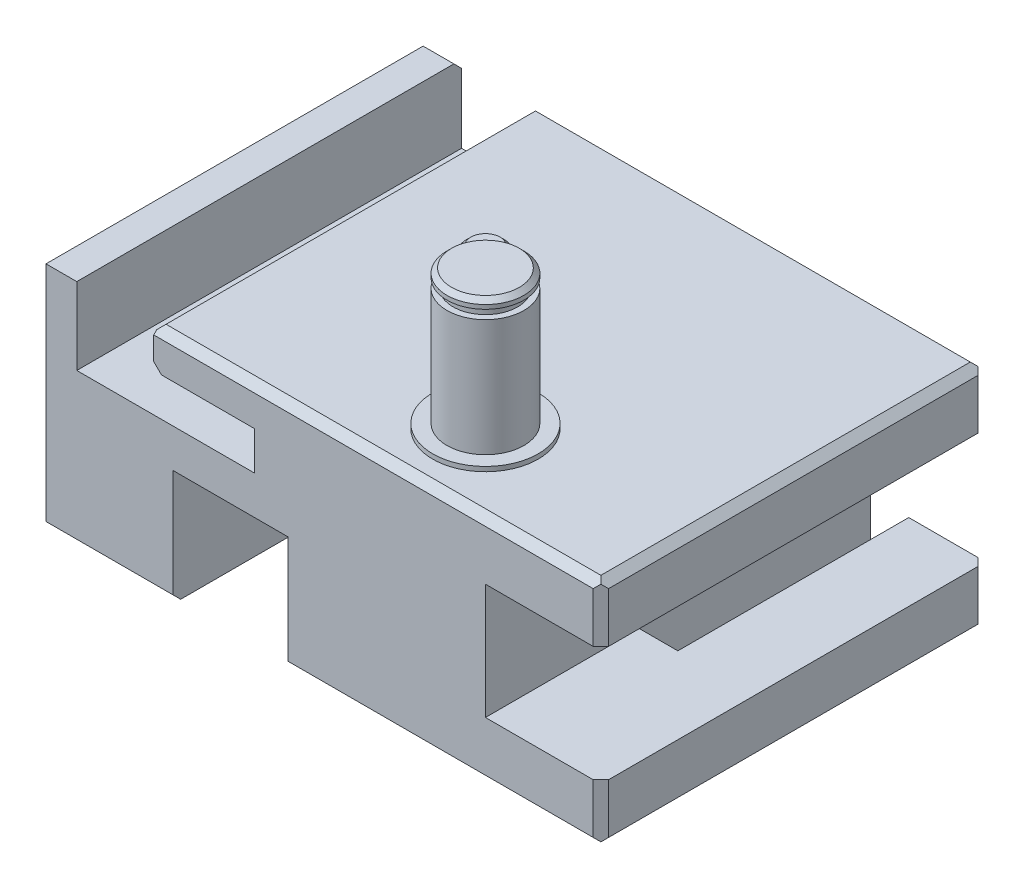
SolidWorks part; units mm, degrees
material "AISI Type A2 Tool Steel"
ref_plane "Front Plane" through (0, 0, 0) normal (0, 0, 1) x (1, 0, 0)
ref_plane "Top Plane" through (0, 0, 0) normal (0, 1, 0) x (1, 0, 0)
ref_plane "Right Plane" through (0, 0, 0) normal (1, 0, 0) x (0, 0, -1)
ref_axis "X-axis" through (-88.99, 0, 0) along (1, 0, 0)
ref_axis "Y-axis" through (0, 55, 0) along (0, -1, 0)
ref_axis "Z-axis" through (0, 0, -88.99) along (0, 0, 1)
sketch "Sketch1" plane through (0, 0, 0) normal (0, 0, 1) x (1, 0, 0)
  line L0 (27.3685, 0) -> (27.3685, 20.8848) construction
  line L1 (0, 0) -> (7.9375, 0)
  line L2 (0, 0) -> (0, 19.05)
  line L3 (0, 19.05) -> (43.2435, 19.05)
  line L4 (43.2435, 0) -> (43.2435, 19.05)
  line L5 (10.7061, 0) -> (10.7061, 19.05) construction
  line L6 (14.6685, 0) -> (14.6685, 19.05) construction
  line L7 (12.6873, -1.5141) -> (12.6873, 17.6649) construction
  line L8 (4.7498, 9.525) -> (20.6248, 9.525)
  line L9 (4.7498, 9.525) -> (4.7498, 6.35)
  line L10 (7.9375, 6.35) -> (7.9375, 0)
  line L11 (17.4371, 6.35) -> (17.4371, 0)
  line L12 (4.7498, 6.35) -> (7.9375, 6.35)
  line L13 (20.6248, 6.35) -> (17.4371, 6.35)
  line L14 (20.6248, 9.525) -> (20.6248, 6.35)
  line L15 (17.4371, 0) -> (43.2435, 0)
  point P16 (12.6873, 9.525)
  point P19 (4.7498, 9.525)
  point P22 (4.7498, 6.35)
  point P25 (7.9375, 6.35)
  dimension "D1" = 19.05
  dimension "D2" = 4.7498
  dimension "D3" = 15.875
  dimension "D4" = 16.6624
  dimension "D5" = 12.7
  dimension "D6" = 14.6812
  dimension "D7" = 15.875
  dimension "D8" = 3.175
  dimension "D9" = 9.525
  dimension "D10" = 4.7498
extrude "Boss-Extrude1" add sketch "Sketch1" along normal blind 31.75
sketch "Sketch3" plane through (0, 0, 0) normal (0, 0, 1) x (1, 0, 0)
  line L0 (6.35, 15.875) -> (14.6685, 15.875)
  line L1 (0, 0) -> (0, 19.05) construction
  line L2 (14.6685, 0) -> (14.6685, 19.05) construction
  line L3 (14.6685, 15.875) -> (14.6685, 12.7)
  line L4 (14.6685, 12.7) -> (0, 12.7)
  line L5 (4.7498, 9.525) -> (20.6248, 9.525) construction
  line L6 (0, 19.05) -> (43.2435, 19.05) construction
  line L7 (6.35, 15.875) -> (6.35, 19.05)
  line L9 (0, 12.7) -> (0, 19.05)
  line L10 (0, 19.05) -> (6.35, 19.05)
  dimension "D1" = 3.175
  dimension "D2" = 3.175
  dimension "D3" = 6.35
extrude "Cut-Extrude2" cut sketch "Sketch3" along normal through all
sketch "Sketch2" plane through (0, 0, 0) normal (0, 0, 1) x (1, 0, 0)
  line L0 (25.3873, 0) -> (43.2435, 9.525)
  line L1 (17.4371, 0) -> (43.2435, 0) construction
  line L2 (43.2435, 0) -> (43.2435, 19.05) construction
  line L3 (43.2435, 19.05) -> (6.35, 19.05) construction
  line L4 (20.6248, 9.525) -> (20.6248, 6.35) construction
  line L5 (25.3873, 0) -> (43.2435, 0)
  line L6 (43.2435, 0) -> (43.2435, 9.525)
  dimension "D1" = 9.525
  dimension "D2" = 4.7625
extrude "Cut-Extrude1" cut sketch "Sketch2" along normal through all
fillet "Fillet1" radius 2.54 3 edges at (25.3873, 0, 15.875) (43.2435, 19.05, 15.875) (43.2435, 9.525, 15.875)
chamfer "Chamfer1" distance 0.635 angle 45 1 edges at (6.35, 15.875, 15.875)
sketch "Sketch5" plane through (0, 19.05, 0) normal (0, 1, 0) x (1, 0, 0)
  line L0 (40.7035, -31.75) -> (6.35, -31.75) construction
  line L1 (43.2435, 0) -> (43.2435, -31.75) construction
  circle A0 centre (27.3685, -25.4) radius 4.3561
  dimension "D3" = 8.7122
  dimension "D1" = 6.35
  dimension "D2" = 15.875
extrude "Boss-Extrude3" add sketch "Sketch5" along normal blind 0.381
sketch "Sketch6" plane through (0, 19.431, 0) normal (0, 1, 0) x (1, 0, 0)
  circle A0 centre (27.3685, -25.4) radius 3.175
  dimension "D1" = 6.35
extrude "Boss-Extrude4" add sketch "Sketch6" along normal blind 11.1125
sketch "Sketch7" plane through (0, 19.05, 0) normal (0, 1, 0) x (1, 0, 0)
  line L0 (27.3685, -25.4) -> (27.3685, -15.875) construction
  line L1 (17.8435, -25.4) -> (27.3685, -25.4) construction
  line L2 (27.3685, -25.4) -> (20.6333, -18.6648) construction
  line L3 (17.8435, -25.4) -> (20.6333, -18.6648) construction
  circle A0 centre (17.8435, -25.4) radius 1.5875 construction
  circle A1 centre (27.3685, -15.875) radius 1.5875 construction
  circle A2 centre (20.6333, -18.6648) radius 1.5875
  circle A25 centre (27.3685, -25.4) radius 3.175 construction
  dimension "D1" = 3.175
  dimension "D4" = 3.175
  dimension "D7" = 3.175
  dimension "D2" = 9.525
  dimension "D3" = 9.525
  dimension "D5" = 45
  dimension "D6" = 9.525
chamfer "Chamfer7" distance 0.381 angle 45 2 edges at (6.35, 19.05, 15.875) (27.3685, 30.5435, 28.575)
sketch "Sketch9" plane through (0, 19.05, 0) normal (0, 1, 0) x (1, 0, 0)
  line L0 (27.3685, 0) -> (43.2435, -19.05)
  line L1 (17.4371, 0) -> (43.2435, 0) construction
  line L2 (43.2435, 0) -> (43.2435, -31.75) construction
  line L5 (40.7035, -31.75) -> (6.731, -31.75) construction
  line L6 (27.3685, 0) -> (43.2435, 0)
  line L7 (43.2435, 0) -> (43.2435, -19.05)
  dimension "D1" = 15.875
  dimension "D2" = 12.7
extrude "Cut-Extrude3" cut sketch "Sketch9" against normal through all
ref_plane "Plane1" through (0, 0, 22.225) normal (0, 0, 1) x (1, 0, 0)
sketch "Sketch12" plane through (0, 0, 0) normal (0, 0, 1) x (1, 0, 0)
  line L0 (40.7035, 19.05) -> (6.731, 19.05) construction
  line L1 (43.2435, 0) -> (24.1935, 0)
  line L2 (43.2435, 0) -> (43.2435, 19.05)
  line L3 (43.2435, 19.05) -> (24.1935, 19.05)
  line L4 (24.1935, 0) -> (24.1935, 19.05)
  line L5 (0, 12.7) -> (0, 0) construction
  dimension "D1" = 19.05
  dimension "D2" = 19.05
  dimension "D3" = 24.1935
extrude "Boss-Extrude9" add sketch "Sketch12" along direction (0, 0, -1) on the side of the normal through all contours L4 L1 L2 L3 region at (33.7185, 9.525, 0)
sketch "Sketch13" plane through (0, 0, 0) normal (0, 0, 1) x (1, 0, 0)
  line L0 (43.2435, 0) -> (43.2435, 19.05) construction
  line L1 (43.2435, 14.2875) -> (36.8935, 14.2875)
  line L2 (43.2435, 14.2875) -> (43.2435, 4.7625)
  line L3 (43.2435, 4.7625) -> (36.8935, 4.7625)
  line L5 (43.2435, 9.525) -> (33.7185, 9.525) construction
  line L10 (17.4371, 0) -> (43.2435, 0) construction
  line L22 (36.8935, 1.5875) -> (36.8935, 4.7625)
  line L23 (36.8935, 1.5875) -> (33.7185, 1.5875)
  line L24 (36.8935, 17.4625) -> (33.7185, 17.4625)
  line L25 (33.7185, 1.5875) -> (33.7185, 17.4625)
  line L26 (36.8935, 1.5875) -> (33.7185, 17.4625) construction
  line L27 (36.8935, 17.4625) -> (33.7185, 1.5875) construction
  line L32 (36.8935, 14.2875) -> (36.8935, 17.4625)
  point P22 (35.306, 9.525)
  dimension "D1" = 9.525
  dimension "D2" = 9.525
  dimension "D3" = 4.7625
  dimension "D4" = 3.175
  dimension "D5" = 15.875
extrude "Cut-Extrude4" cut sketch "Sketch13" along normal through all
chamfer "Chamfer6" distance 0.635 angle 45 4 edges at (43.2435, 2.3813, 0) (43.2435, 0, 15.875) (43.2435, 16.6688, 0) (43.2435, 19.05, 15.875)
sketch "Sketch15" plane through (0, 0, 0) normal (0, 1, 0) x (1, 0, 0)
  line L0 (42.6085, 0) -> (6.731, 0) construction
  line L1 (42.6085, 0) -> (6.731, 0)
  point P0 (27.3685, -25.4)
ref_plane "Plane2" through (0, 0, 25.4) normal (0, 0, 1) x (1, 0, 0)
sketch "Sketch16" plane through (0, 0, 25.4) normal (0, 0, 1) x (1, 0, 0)
  line L0 (27.3685, 30.1625) -> (27.3685, 33.4145) construction
  line L1 (24.1935, 30.1625) -> (30.5435, 30.1625) construction
  line L3 (24.1935, 30.1625) -> (24.1935, 19.431) construction
  line L4 (31.7246, 19.431) -> (23.0124, 19.431) construction
  line L5 (23.6855, 29.083) -> (24.7015, 29.083)
  line L6 (23.6855, 29.083) -> (23.6855, 29.8196)
  line L7 (23.6855, 29.8196) -> (24.7015, 29.8196)
  line L8 (24.7015, 29.083) -> (24.7015, 29.8196)
  line L9 (23.6855, 29.083) -> (24.7015, 29.8196) construction
  line L10 (23.6855, 29.8196) -> (24.7015, 29.083) construction
  point P6 (24.1935, 29.4513)
  dimension "D1" = 1.016
  dimension "D2" = 0.7366
  dimension "D3" = 9.652
revolve "Cut-Revolve1" cut sketch "Sketch16" angle 360 about L0
extrude "Boss-Extrude11" add sketch "Sketch7" along normal blind 6.35
chamfer "Chamfer9" distance 0.381 angle 45 2 edges at (20.6333, 25.4, 20.2523) (20.6333, 19.05, 17.0773)
sketch "Sketch18" plane through (0, 0, 31.75) normal (0, 0, 1) x (1, 0, 0)
  line L0 (7.9375, 0) -> (7.9375, 6.35) construction
  line L1 (7.9375, 6.096) -> (4.1275, 6.096)
  line L2 (7.9375, 6.096) -> (7.9375, 9.906)
  line L3 (7.9375, 9.906) -> (4.1275, 9.906)
  line L4 (4.1275, 6.096) -> (4.1275, 9.906)
  line L5 (17.4371, 6.35) -> (17.4371, 0) construction
  line L6 (17.4371, 6.096) -> (21.2471, 6.096)
  line L7 (17.4371, 6.096) -> (17.4371, 9.906)
  line L8 (17.4371, 9.906) -> (21.2471, 9.906)
  line L9 (21.2471, 6.096) -> (21.2471, 9.906)
  line L10 (36.8935, 4.7625) -> (43.2435, 4.7625) construction
  line L11 (37.2745, 4.7625) -> (33.4645, 4.7625)
  line L12 (37.2745, 4.7625) -> (37.2745, 0.9525)
  line L13 (37.2745, 0.9525) -> (33.4645, 0.9525)
  line L14 (33.4645, 4.7625) -> (33.4645, 0.9525)
  line L15 (43.2435, 14.2875) -> (36.8935, 14.2875) construction
  line L16 (37.2745, 14.2875) -> (33.4645, 14.2875)
  line L17 (37.2745, 14.2875) -> (37.2745, 18.0975)
  line L18 (37.2745, 18.0975) -> (33.4645, 18.0975)
  line L19 (33.4645, 14.2875) -> (33.4645, 18.0975)
  line L20 (0, 12.7) -> (14.6685, 12.7) construction
  line L21 (43.2435, 14.2875) -> (43.2435, 18.415) construction
  dimension "D1" = 3.81
  dimension "D2" = 3.81
  dimension "D3" = 2.794
  dimension "D4" = 5.969
  dimension "D5" = 3.81
  dimension "D6" = 3.81
extrude "Boss-Extrude12" add sketch "Sketch18" against normal blind 12.7
sketch "Sketch19" plane through (0, 12.7, 0) normal (0, 1, 0) x (1, 0, 0)
  line L0 (42.6085, -31.75) -> (6.731, -31.75) construction
  line L1 (43.2435, -0.635) -> (43.2435, -31.75) construction
  line L2 (7.1755, -22.098) -> (10.2235, -22.098)
  arc A0 (7.1755, -22.098) -> (10.2235, -22.098) centre (8.6995, -22.098) ccw
  dimension "D1" = 3.048
  dimension "D2" = 9.652
  dimension "D3" = 34.544
extrude "Boss-Extrude13" add sketch "Sketch19" along normal blind 0.635
chamfer "Chamfer10" distance 0.889 angle 35 1 edges at (8.6995, 12.7, 22.098) first distance on face at (7.3342, 12.7, 15.875)
sketch "Sketch20" plane through (0, 0, 31.75) normal (0, 0, 1) x (1, 0, 0)
  line L0 (42.6085, 19.05) -> (6.731, 19.05) construction
  line L1 (0, 0) -> (-3.175, 0)
  line L2 (0, 0) -> (0, 19.05)
  line L3 (0, 19.05) -> (-3.175, 19.05)
  line L4 (-3.175, 0) -> (-3.175, 19.05)
  dimension "D1" = 3.175
extrude "Boss-Extrude14" add sketch "Sketch20" against normal up to surface (31.75 mm away) up to face at (20.8729, 9.6569, 0)
chamfer "Chamfer11" distance 0.635 angle 45 13 edges at (-3.175, 19.05, 15.875) (-3.175, 0, 15.875) (24.6698, 19.05, 0) (30.0228, 0, 0) (30.0228, 0, 31.75) (24.6698, 19.05, 31.75) (-1.5875, 19.05, 0) (2.3813, 0, 0) (2.3813, 0, 31.75) (43.2435, 2.6987, 31.75) (43.2435, 16.3513, 31.75) (-3.175, 9.525, 0) (-3.175, 9.525, 31.75)
